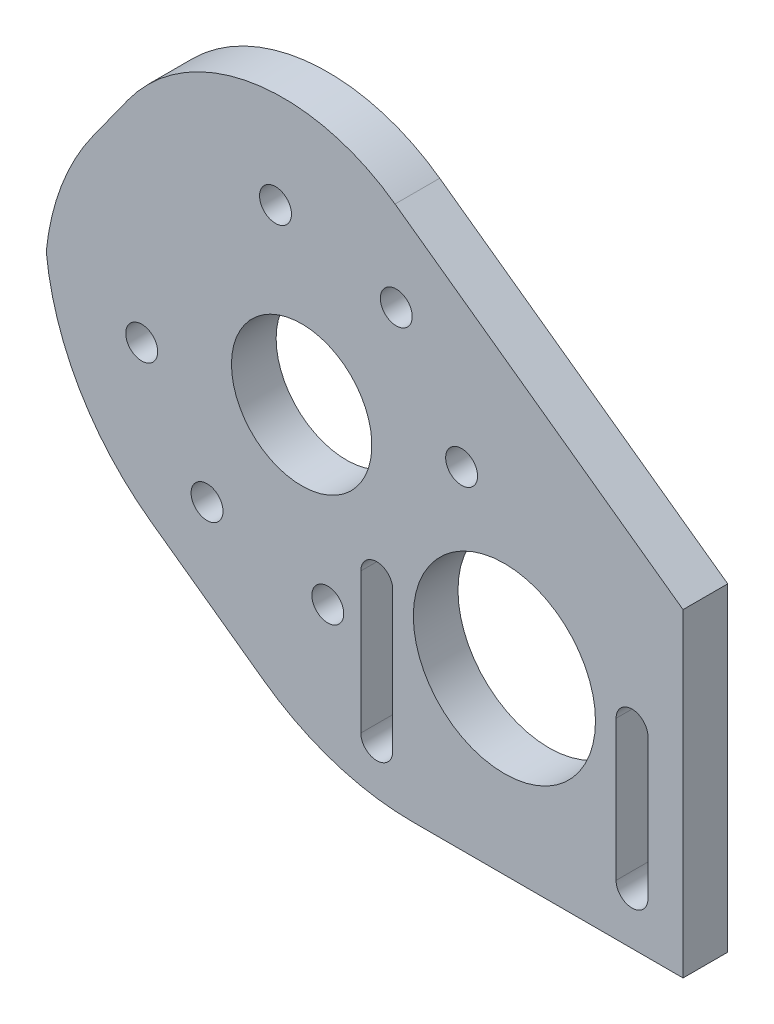
SolidWorks part; units mm, degrees
ref_plane "Front Plane" through (0, 0, 0) normal (0, 0, 1) x (1, 0, 0)
ref_plane "Top Plane" through (0, 0, 0) normal (0, 1, 0) x (1, 0, 0)
ref_plane "Right Plane" through (0, 0, 0) normal (1, 0, 0) x (0, 0, -1)
sketch "Sketch1" plane through (0, 0, 0) normal (0, 0, 1) x (1, 0, 0)
  line L1 (0, 0) -> (100, 0)
  line L2 (0, 0) -> (0, 100)
  line L3 (0, 100) -> (100, 100)
  line L4 (100, 0) -> (100, 100)
  dimension "D1" = 100
  dimension "D2" = 100
extrude "Boss-Extrude1" add sketch "Sketch1" along normal blind 7 contours L3 L4 L1 L2
sketch "Sketch2" plane through (0, 0, 7) normal (0, 0, 1) x (1, 0, 0)
  line L1 (0, 100) -> (100, 100) construction
  line L2 (0, 0) -> (100, 0) construction
  line L3 (0, 50) -> (100, 50) construction
  line L4 (0, 0) -> (0, 100) construction
  line L5 (100, 0) -> (100, 100) construction
  line L6 (52, 30) -> (52, 8) construction
  line L7 (54.5, 30) -> (54.5, 8)
  line L8 (49.5, 30) -> (49.5, 8)
  line L9 (92, 30) -> (92, 8) construction
  line L10 (94.5, 30) -> (94.5, 8)
  line L11 (89.5, 30) -> (89.5, 8)
  line L12 (100, 0) -> (100, 100) construction
  circle A0 centre (72, 28) radius 14.275
  arc A5 (54.5, 30) -> (49.5, 30) centre (52, 30) ccw
  arc A6 (49.5, 8) -> (54.5, 8) centre (52, 8) ccw
  arc A7 (94.5, 30) -> (89.5, 30) centre (92, 30) ccw
  arc A8 (89.5, 8) -> (94.5, 8) centre (92, 8) ccw
  point P22 (52, 19)
  point P27 (92, 19)
  dimension "D1" = 28.55
  dimension "D2" = 40
  dimension "D3" = 8
  dimension "D4" = 28
  dimension "D7" = 70
  dimension "D8" = 8
  dimension "D11" = 8
  dimension "D12" = 70
  dimension "D14" = 5
  dimension "D15" = 5
extrude "Cut-Extrude1" cut sketch "Sketch2" against normal through all
sketch "Sketch3" plane through (0, 0, 0) normal (0, 0, -1) x (-1, 0, 0)
  circle A0 centre (-72, 28) radius 14.275 construction
  circle A1 centre (-40.2255, 47.9156) radius 11
  dimension "D2" = 22
  dimension "D1" = 37.5
extrude "Cut-Extrude2" cut sketch "Sketch3" against normal blind 10
sketch "Sketch6" plane through (0, 0, 0) normal (0, 0, -1) x (-1, 0, 0)
  circle A6 centre (-15.1581, 43.8189) radius 2.5
  circle A7 centre (-36.1288, 72.9831) radius 2.5
  circle A8 centre (-25.397, 27.2934) radius 2.5
  circle A9 centre (-44.3223, 22.8482) radius 2.5
  circle A10 centre (-55.054, 68.5378) radius 2.5
  circle A11 centre (-65.293, 52.0124) radius 2.5
  circle A12 centre (-25.397, 27.2934) radius 2.0193 construction
  circle A13 centre (-44.3223, 22.8482) radius 2.0193 construction
  circle A14 centre (-65.293, 52.0124) radius 2.0193 construction
  circle A15 centre (-55.054, 68.5378) radius 2.0193 construction
  circle A16 centre (-36.1288, 72.9831) radius 2.0193 construction
  circle A17 centre (-15.1581, 43.8189) radius 2.0193 construction
  point P0 (0, 0)
  dimension "D1" = 5
  dimension "D2" = 5
  dimension "D3" = 5
  dimension "D4" = 5
  dimension "D5" = 5
  dimension "D6" = 5
extrude "Cut-Extrude3" cut sketch "Sketch6" against normal through all
sketch "Sketch7" plane through (0, 0, 0) normal (0, 0, -1) x (-1, 0, 0)
  line L0 (-100, 50) -> (-30.509, 100)
  line L1 (-100, 0) -> (-100, 100) construction
  line L3 (-30.509, 100) -> (0, 57.598)
  line L4 (0, 0) -> (0, 100) construction
  line L5 (0, 57.598) -> (0, 32.1949)
  line L6 (0, 32.1949) -> (-44.7451, 0)
  line L7 (0, 0) -> (-100, 0) construction
  line L8 (-44.7451, -2.0672) -> (0, -21.6596)
  line L9 (0, -21.6596) -> (29.3124, 38.0432)
  line L10 (29.3124, 38.0432) -> (18.8626, 143.2004)
  line L11 (18.8626, 143.2004) -> (-133.2592, 128.0837)
  line L12 (-133.2592, 128.0837) -> (-100, 50)
extrude "Cut-Extrude4" cut sketch "Sketch7" against normal through all and the other way through all
fillet "Fillet1" radius 30 1 edges at (30.509, 100, 3.5)
fillet "Fillet2" radius 40 3 edges at (44.7451, 0, 3.5) (0, 32.1949, 3.5) (0, 57.598, 3.5)
